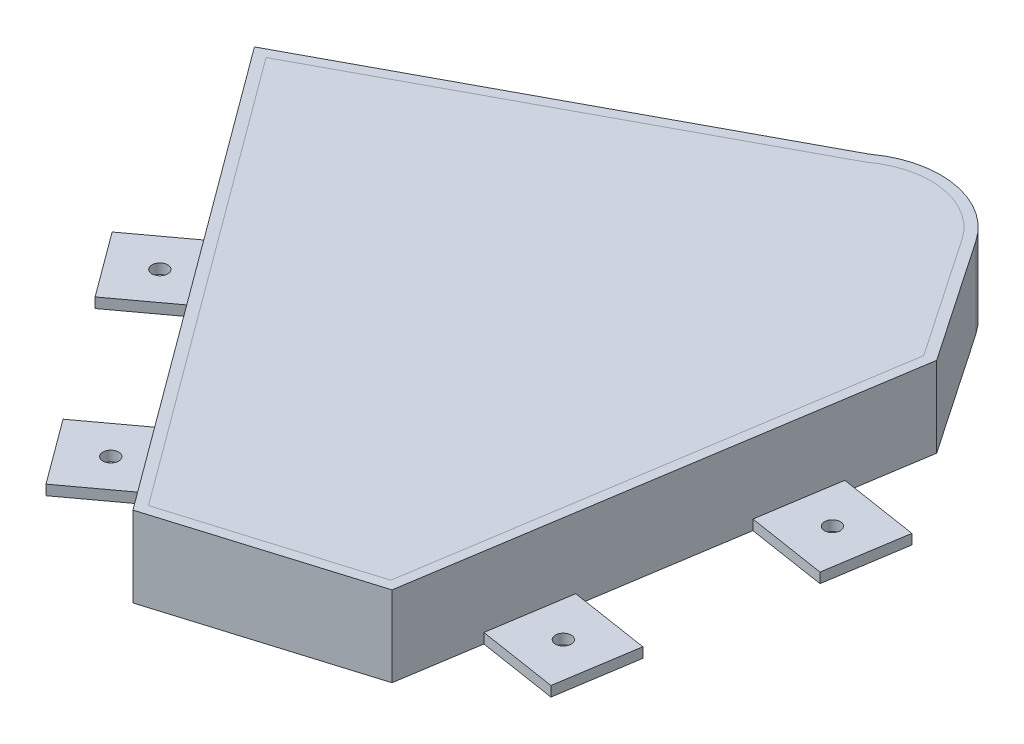
SolidWorks part; units mm, degrees
ref_plane "Front Plane" through (0, 0, 0) normal (0, 0, 1) x (1, 0, 0)
ref_plane "Top Plane" through (0, 0, 0) normal (0, 1, 0) x (1, 0, 0)
ref_plane "Right Plane" through (0, 0, 0) normal (1, 0, 0) x (0, 0, -1)
sketch "Sketch1" plane through (0, 0, 0) normal (0, 1, 0) x (1, 0, 0)
  line L0 (-3.4248, 107.9175) -> (-126.7584, 41.8027)
  line L1 (-126.7584, 41.8027) -> (-22.7865, -99.2856)
  line L2 (-22.7865, -99.2856) -> (35.8898, -81.442)
  line L3 (35.8898, -81.442) -> (58.6084, 64.1322)
  line L4 (58.6084, 64.1322) -> (32.8788, 101.9377)
  arc A0 (32.8788, 101.9377) -> (-3.4248, 107.9175) centre (11.8805, 87.6466) ccw
  dimension "D1" = 175.26
extrude "Boss-Extrude1" add sketch "Sketch1" along normal blind 2.54
sketch "Sketch2" plane through (0, 2.54, 0) normal (0, 1, 0) x (1, 0, 0)
  line L0 (-126.7584, 41.8027) -> (-22.7865, -99.2856)
  line L1 (-22.7865, -99.2856) -> (35.8898, -81.442)
  line L2 (35.8898, -81.442) -> (58.6084, 64.1322)
  line L3 (58.6084, 64.1322) -> (32.8788, 101.9377)
  line L4 (-3.4248, 107.9175) -> (-126.7584, 41.8027)
  line L5 (-5.1352, 110.6031) -> (-131.4885, 42.8695)
  line L6 (-131.4885, 42.8695) -> (-24.0106, -102.9764)
  line L7 (-24.0106, -102.9764) -> (38.7196, -83.9)
  line L8 (38.7196, -83.9) -> (61.9388, 64.8817)
  line L9 (61.9388, 64.8817) -> (35.5035, 103.724)
  arc A0 (32.8788, 101.9377) -> (-3.4248, 107.9175) centre (11.8805, 87.6466) ccw
  arc A1 (35.5035, 103.724) -> (-5.1352, 110.6031) centre (11.8805, 87.6466) ccw
  dimension "D1" = 3.175
extrude "Boss-Extrude2" add sketch "Sketch2" against normal blind 25.4 separate body
sketch "Sketch3" plane through (-64.7393, 0, 47.7082) normal (-0.805, 0, 0.5932) x (0.5932, 0, 0.805)
  line L0 (-112.5157, -22.86) -> (68.6542, -22.86) construction
  line L1 (-68.0657, -22.86) -> (-42.6657, -22.86)
  line L2 (-68.0657, -22.86) -> (-68.0657, -19.685)
  line L3 (-68.0657, -19.685) -> (-42.6657, -19.685)
  line L4 (-42.6657, -22.86) -> (-42.6657, -19.685)
  line L5 (68.6542, -22.86) -> (68.6542, 2.54) construction
  line L6 (5.1542, -22.86) -> (30.5542, -22.86)
  line L7 (5.1542, -22.86) -> (5.1542, -19.685)
  line L8 (5.1542, -19.685) -> (30.5542, -19.685)
  line L9 (30.5542, -22.86) -> (30.5542, -19.685)
  line L10 (-112.5157, -22.86) -> (-112.5157, 2.54) construction
  dimension "D1" = 3.175
  dimension "D2" = 25.4
  dimension "D3" = 3.175
  dimension "D4" = 25.4
  dimension "D5" = 38.1
  dimension "D6" = 44.45
extrude "Boss-Extrude3" add sketch "Sketch3" along normal blind 25.4
sketch "Sketch4" plane through (50.5813, 0, 7.8938) normal (0.988, 0, 0.1542) x (0.1542, 0, -0.988)
  line L0 (-76.9262, -22.86) -> (73.6565, -22.86) construction
  line L1 (-51.5262, -22.86) -> (-26.1262, -22.86)
  line L2 (-51.5262, -22.86) -> (-51.5262, -19.685)
  line L3 (-51.5262, -19.685) -> (-26.1262, -19.685)
  line L4 (-26.1262, -22.86) -> (-26.1262, -19.685)
  line L5 (-76.9262, -22.86) -> (-76.9262, 2.54) construction
  line L6 (22.8565, -22.86) -> (48.2565, -22.86)
  line L7 (22.8565, -22.86) -> (22.8565, -19.685)
  line L8 (22.8565, -19.685) -> (48.2565, -19.685)
  line L9 (48.2565, -22.86) -> (48.2565, -19.685)
  line L10 (73.6565, -22.86) -> (73.6565, 2.54) construction
  dimension "D1" = 3.175
  dimension "D2" = 25.4
  dimension "D3" = 3.175
  dimension "D4" = 25.4
  dimension "D5" = 25.4
  dimension "D6" = 25.4
extrude "Boss-Extrude4" add sketch "Sketch4" along normal blind 25.4
sketch "Sketch5" plane through (0, -19.685, 0) normal (0, 1, 0) x (1, 0, 0)
  line L0 (-115.3426, -0.448) -> (-100.2742, -20.8956) construction
  line L1 (-125.5664, -7.9822) -> (-105.1188, 7.0862) construction
  line L2 (-110.498, -28.4298) -> (-90.0504, -13.3614) construction
  line L3 (-71.9054, -59.3917) -> (-56.837, -79.8392) construction
  line L4 (-82.1292, -66.9259) -> (-61.6816, -51.8575) construction
  line L5 (-67.0608, -87.3734) -> (-46.6132, -72.305) construction
  line L6 (59.1009, -35.6658) -> (55.1843, -60.7621) construction
  line L7 (71.649, -37.6241) -> (46.5528, -33.7075) construction
  line L8 (67.7324, -62.7203) -> (42.6362, -58.8038) construction
  line L9 (70.5704, 37.8272) -> (66.6538, 12.731) construction
  line L10 (83.1185, 35.869) -> (58.0223, 39.7855) construction
  line L11 (79.2019, 10.7727) -> (54.1057, 14.6893) construction
  circle A0 centre (-107.8084, -10.6718) radius 2.4892
  circle A1 centre (-64.3712, -69.6155) radius 2.4892
  circle A2 centre (57.1426, -48.2139) radius 2.4892
  circle A3 centre (68.6121, 25.2791) radius 2.4892
  dimension "D1" = 4.9784
  dimension "D2" = 4.9784
  dimension "D3" = 4.9784
  dimension "D4" = 4.9784
extrude "Cut-Extrude1" cut sketch "Sketch5" against normal up to next (3.175 mm away)
